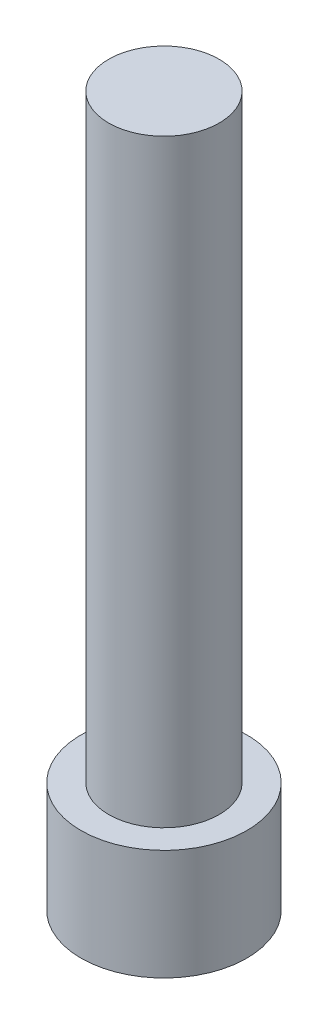
SolidWorks part; units mm, degrees
ref_plane "Front Plane" through (0, 0, 0) normal (0, 0, 1) x (1, 0, 0)
ref_plane "Top Plane" through (0, 0, 0) normal (0, 1, 0) x (1, 0, 0)
ref_plane "Right Plane" through (0, 0, 0) normal (1, 0, 0) x (0, 0, -1)
sketch "Sketch1" plane through (0, 0, 0) normal (0, 1, 0) x (1, 0, 0)
  circle A0 centre (0, 0) radius 9
extrude "Boss-Extrude1" add sketch "Sketch1" along normal blind 12
sketch "Sketch2" plane through (0, 12, 0) normal (0, 1, 0) x (1, 0, 0)
  circle A0 centre (0, 0) radius 6
extrude "Boss-Extrude2" add sketch "Sketch2" along normal blind 65
